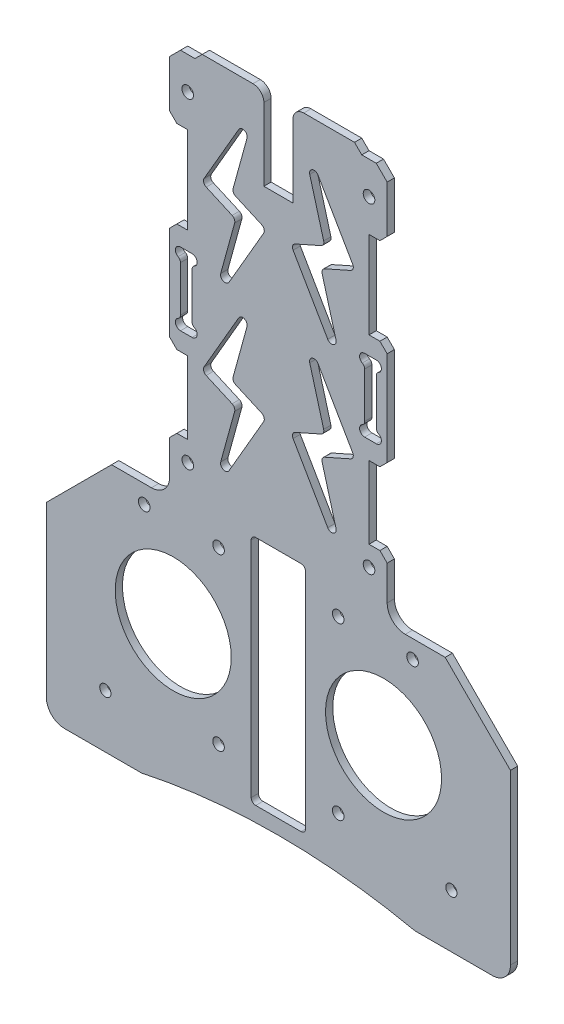
SolidWorks part; units mm, degrees
material "Thornel Mat VMA"
ref_plane "前视基准面" through (0, 0, 0) normal (0, 0, 1) x (1, 0, 0)
ref_plane "上视基准面" through (0, 0, 0) normal (0, 1, 0) x (1, 0, 0)
ref_plane "右视基准面" through (0, 0, 0) normal (1, 0, 0) x (0, 0, -1)
sketch "草图1" plane through (0, 0, 0) normal (0, 0, 1) x (1, 0, 0)
  line L1 (64, -90) -> (-64, -90)
  line L2 (64, -90) -> (64, 90)
  line L3 (64, 90) -> (-64, 90)
  line L4 (-64, -90) -> (-64, 90)
  line L5 (64, -90) -> (-64, 90) construction
  line L6 (64, 90) -> (-64, -90) construction
  point P0 (0, 0)
  dimension "D1" = 180
  dimension "D2" = 128
extrude "凸台-拉伸1" add sketch "草图1" along normal blind 2
sketch "草图3" plane through (0, 0, 2) normal (0, 0, 1) x (1, 0, 0)
  line L0 (-64, 0) -> (0, 0) construction
  line L1 (-64, 90) -> (-64, -90) construction
  line L2 (0, 0) -> (0, -90) construction
  line L3 (-64, -90) -> (64, -90) construction
  line L4 (64, 90) -> (-64, 90) construction
  line L5 (30, 90) -> (30, -20.5)
  line L6 (-64, 90) -> (-30, 90)
  line L7 (-64, 90) -> (-64, -20.5)
  line L8 (-64, -20.5) -> (-30, -20.5)
  line L9 (-30, 90) -> (-30, -20.5)
  line L10 (64, -20.5) -> (30, -20.5)
  line L11 (64, 90) -> (64, -20.5)
  line L12 (64, 90) -> (30, 90)
  line L14 (7.5, -82) -> (-7.5, -82)
  line L15 (7.5, -82) -> (7.5, -18)
  line L16 (7.5, -18) -> (-7.5, -18)
  line L17 (-7.5, -82) -> (-7.5, -18)
  line L18 (7.5, -82) -> (-7.5, -18) construction
  line L19 (7.5, -18) -> (-7.5, -82) construction
  circle A0 centre (-29, -50) radius 16
  circle A1 centre (29, -50) radius 16
  point P23 (0, -50)
  dimension "D1" = 32
  dimension "D2" = 140
  dimension "D3" = 58
  dimension "D4" = 60
  dimension "D5" = 110.5
  dimension "D6" = 8
  dimension "D7" = 64
  dimension "D8" = 15
extrude "切除-拉伸1" cut sketch "草图3" against normal blind 10
fillet "圆角2" radius 5 4 edges at (64, -90, 1) (-30, -20.5, 1) (30, -20.5, 1) (-64, -90, 1)
sketch "草图4" plane through (0, 0, 2) normal (0, 0, 1) x (1, 0, 0)
  line L0 (-30, 0) -> (0, 0) construction
  line L1 (-30, -15.5) -> (-30, 90) construction
  line L2 (0, 0) -> (0, -90) construction
  line L3 (-59, -90) -> (59, -90) construction
  line L4 (-29, -50) -> (0, -50) construction
  line L6 (-64, -20.5) -> (-35, -20.5) construction
  circle A0 centre (-37, -25.5) radius 1.6
  circle A5 centre (37, -25.5) radius 1.6
  dimension "D1" = 3.2
  dimension "D5" = 5
  dimension "D6" = 7
extrude "切除-拉伸2" cut sketch "草图4" against normal through all
sketch "草图7" plane through (0, 0, 0) normal (0, 0, -1) x (-1, 0, 0)
  line L0 (0, 0) -> (0, 90) construction
  line L1 (-30, 90) -> (-21, 90)
  line L2 (-30, 90) -> (-30, 88)
  line L3 (-30, 88) -> (-21, 88)
  line L4 (-21, 90) -> (-21, 88)
  line L5 (-30, 90) -> (30, 90) construction
  line L6 (21, 90) -> (21, 88)
  line L7 (30, 88) -> (21, 88)
  line L8 (30, 90) -> (30, 88)
  line L9 (30, 90) -> (21, 90)
  line L10 (-25, 79) -> (0, 79) construction
  line L11 (59, -90) -> (-59, -90) construction
  line L12 (-30, 90) -> (-30, -15.5) construction
  line L13 (-30, 70) -> (-25, 70)
  line L14 (-30, 70) -> (-30, 46)
  line L15 (-30, 46) -> (-25, 46)
  line L16 (-25, 70) -> (-25, 46)
  line L17 (25, 16) -> (25, -4)
  line L18 (-30, 16) -> (-25, 16)
  line L19 (-30, 16) -> (-30, -4)
  line L20 (-30, -4) -> (-25, -4)
  line L21 (-25, 16) -> (-25, -4)
  line L22 (30, -4) -> (25, -4)
  line L23 (30, 16) -> (30, -4)
  line L24 (30, 16) -> (25, 16)
  line L25 (25, 70) -> (25, 46)
  line L26 (30, 46) -> (25, 46)
  line L27 (30, 70) -> (30, 46)
  line L28 (30, 70) -> (25, 70)
  line L29 (23.8, 41) -> (23.8, 21)
  line L30 (-27, 41) -> (-23.8, 41)
  line L31 (-27, 41) -> (-27, 21)
  line L32 (-27, 21) -> (-23.8, 21)
  line L33 (-23.8, 41) -> (-23.8, 21)
  line L34 (27, 21) -> (23.8, 21)
  line L35 (27, 41) -> (27, 21)
  line L36 (27, 41) -> (23.8, 41)
  line L37 (-35, -20.5) -> (-64, -20.5) construction
  circle A0 centre (-25, 79) radius 1.6
  circle A1 centre (25, 79) radius 1.6
  circle A2 centre (0, -266) radius 180
  circle A3 centre (25, -9.5) radius 1.6
  circle A4 centre (-25, -9.5) radius 1.6
  dimension "D3" = 3.2
  dimension "D4" = 50
  dimension "D5" = 11
  dimension "D6" = 360
  dimension "D1" = 42
  dimension "D2" = 2
  dimension "D7" = 176
  dimension "D8" = 50
  dimension "D9" = 50
  dimension "D10" = 20
  dimension "D11" = 24
  dimension "D12" = 20
  dimension "D13" = 30
  dimension "D14" = 3.2
  dimension "D15" = 3
  dimension "D16" = 20
  dimension "D17" = 5
  dimension "D19" = 11
  dimension "D18" = 2
extrude "切除-拉伸3" cut sketch "草图7" against normal blind 8
chamfer "倒角1" distance 2 angle 45 2 edges at (21, 88, 1) (-21, 88, 1)
chamfer "倒角2" distance 18 angle 45 2 edges at (-64, -20.5, 1) (64, -20.5, 1)
chamfer "倒角3" distance 3 angle 45 2 edges at (30, 88, 1) (-30, 88, 1)
chamfer "倒角4" distance 2 angle 45 8 edges at (30, 70, 1) (30, 46, 1) (30, 16, 1) (30, -4, 1) (-30, -4, 1) (-30, 16, 1) (-30, 46, 1) (-30, 70, 1)
sketch "草图10" plane through (0, 0, 0) normal (0, 0, -1) x (-1, 0, 0)
  line L0 (-27, 41) -> (-27, 21) construction
  line L1 (-23.8, 21) -> (-23.8, 41) construction
  line L2 (25, 0) -> (0, 0) construction
  line L3 (25, 16) -> (25, -4) construction
  line L4 (0, 0) -> (0, 90) construction
  line L5 (-21, 90) -> (21, 90) construction
  circle A0 centre (-27, 22.4) radius 1.4
  circle A1 centre (-23.8, 22.4) radius 1.4
  circle A2 centre (-27, 39.6) radius 1.4
  circle A3 centre (-23.8, 39.6) radius 1.4
  circle A4 centre (23.8, 39.6) radius 1.4
  circle A5 centre (27, 39.6) radius 1.4
  circle A6 centre (23.8, 22.4) radius 1.4
  circle A7 centre (27, 22.4) radius 1.4
  dimension "D1" = 2.8
  dimension "D2" = 2.8
  dimension "D3" = 2.8
  dimension "D4" = 2.8
extrude "切除-拉伸4" cut sketch "草图10" against normal through all
sketch "草图11" plane through (0, 0, 2) normal (0, 0, 1) x (1, 0, 0)
  line L0 (6.0787, 40.5023) -> (21.1898, 14.42)
  line L1 (21.1898, 14.42) -> (11.7724, 10.2382)
  line L2 (11.7724, 10.2382) -> (18.4681, -14.11)
  line L3 (18.4681, -14.11) -> (3.357, 11.9723)
  line L4 (3.357, 11.9723) -> (12.7744, 16.154)
  line L5 (12.7744, 16.154) -> (6.0787, 40.5023)
  line L6 (12.7744, 16.154) -> (11.7724, 10.2382) construction
  line L7 (0, -18) -> (0, 0) construction
  line L8 (7.5, -18) -> (-7.5, -18) construction
  line L9 (-18.4681, -14.11) -> (-3.357, 11.9723)
  line L10 (-11.7724, 10.2382) -> (-18.4681, -14.11)
  line L11 (-21.1898, 14.42) -> (-11.7724, 10.2382)
  line L12 (-12.7744, 16.154) -> (-6.0787, 40.5023)
  line L13 (-6.0787, 40.5023) -> (-21.1898, 14.42)
  line L14 (-3.357, 11.9723) -> (-12.7744, 16.154)
  line L15 (-6.0787, 85.5023) -> (-21.1898, 59.42)
  line L16 (-12.7744, 61.154) -> (-6.0787, 85.5023)
  line L17 (-3.357, 56.9723) -> (-12.7744, 61.154)
  line L18 (-18.4681, 30.89) -> (-3.357, 56.9723)
  line L19 (-11.7724, 55.2382) -> (-18.4681, 30.89)
  line L20 (-21.1898, 59.42) -> (-11.7724, 55.2382)
  line L21 (12.7744, 61.154) -> (6.0787, 85.5023)
  line L22 (6.0787, 85.5023) -> (21.1898, 59.42)
  line L23 (21.1898, 59.42) -> (11.7724, 55.2382)
  line L24 (11.7724, 55.2382) -> (18.4681, 30.89)
  line L25 (18.4681, 30.89) -> (3.357, 56.9723)
  line L26 (3.357, 56.9723) -> (12.7744, 61.154)
  circle A0 centre (12.2734, 13.1961) radius 3 construction
  circle A1 centre (12.2734, 13.1961) radius 9 construction
  circle A2 centre (12.2734, 13.1961) radius 28 construction
  dimension "D2" = 6
  dimension "D3" = 18
  dimension "D4" = 56
  dimension "D1" = 5
  dimension "D5" = 2
extrude "切除-拉伸5" cut sketch "草图11" against normal through all
fillet "圆角3" radius 1.25 36 edges at (7.5, -18, 1) (7.5, -82, 1) (-7.5, -82, 1) (-7.5, -18, 1) (27, 38.2, 1) (27, 23.8, 1) (23.8, 23.8, 1) (23.8, 38.2, 1) (-27, 38.2, 1) (-23.8, 38.2, 1) (-23.8, 23.8, 1) (-27, 23.8, 1) (21.1898, 14.42, 1) (11.7724, 10.2382, 1) (18.4681, -14.11, 1) (3.357, 11.9723, 1) (12.7744, 16.154, 1) (6.0787, 40.5023, 1) (-21.1898, 14.42, 1) (-6.0787, 40.5023, 1) (-12.7744, 16.154, 1) (-3.357, 11.9723, 1) (-18.4681, -14.11, 1) (-11.7724, 10.2382, 1) (11.7724, 55.2382, 1) (18.4681, 30.89, 1) (3.357, 56.9723, 1) (12.7744, 61.154, 1) (6.0787, 85.5023, 1) (21.1898, 59.42, 1) (-12.7744, 61.154, 1) (-3.357, 56.9723, 1) (-18.4681, 30.89, 1) (-11.7724, 55.2382, 1) (-21.1898, 59.42, 1) (-6.0787, 85.5023, 1)
sketch "草图12" plane through (0, 0, 2) normal (0, 0, 1) x (1, 0, 0)
  line L0 (0, 0) -> (0, -86) construction
  line L1 (-59, -90) -> (-37.7359, -90) construction
  arc A0 (37.7359, -90) -> (-37.7359, -90) centre (0, -266) ccw construction
  circle A1 centre (-16.5, -72.5) radius 1.6
  circle A2 centre (16.5, -72.5) radius 1.6
  circle A3 centre (16.5, -25.5) radius 1.6
  circle A4 centre (-16.5, -25.5) radius 1.6
  dimension "D1" = 3.2
  dimension "D3" = 33
  dimension "D5" = 47
  dimension "D2" = 17.5
  dimension "D4" = 2
extrude "切除-拉伸6" cut sketch "草图12" against normal blind 10
sketch "草图13" plane through (0, 0, 0) normal (0, 0, -1) x (-1, 0, 0)
  line L0 (0, -69.5791) -> (0, -80.0537) construction
  circle A0 centre (-47.7164, -75.2581) radius 1.55
  circle A1 centre (47.7164, -75.2581) radius 1.55
  dimension "D1" = 3.1
extrude "切除-拉伸7" cut sketch "草图13" against normal blind 10
sketch "草图14" plane through (0, 0, 2) normal (0, 0, 1) x (1, 0, 0)
  line L1 (0, 100.933) -> (0, 68.1768) construction
  line L4 (0, 90) -> (4, 90)
  line L5 (21, 90) -> (-21, 90) construction
  line L6 (4, 90) -> (4, 67)
  line L7 (4, 67) -> (-4, 67)
  line L8 (-4, 67) -> (-4, 90)
  line L9 (-4, 90) -> (0, 90)
  dimension "D1" = 23
extrude "切除-拉伸8" cut sketch "草图14" against normal blind 10
fillet "圆角4" radius 3 2 edges at (-4, 90, 1) (4, 90, 1)
